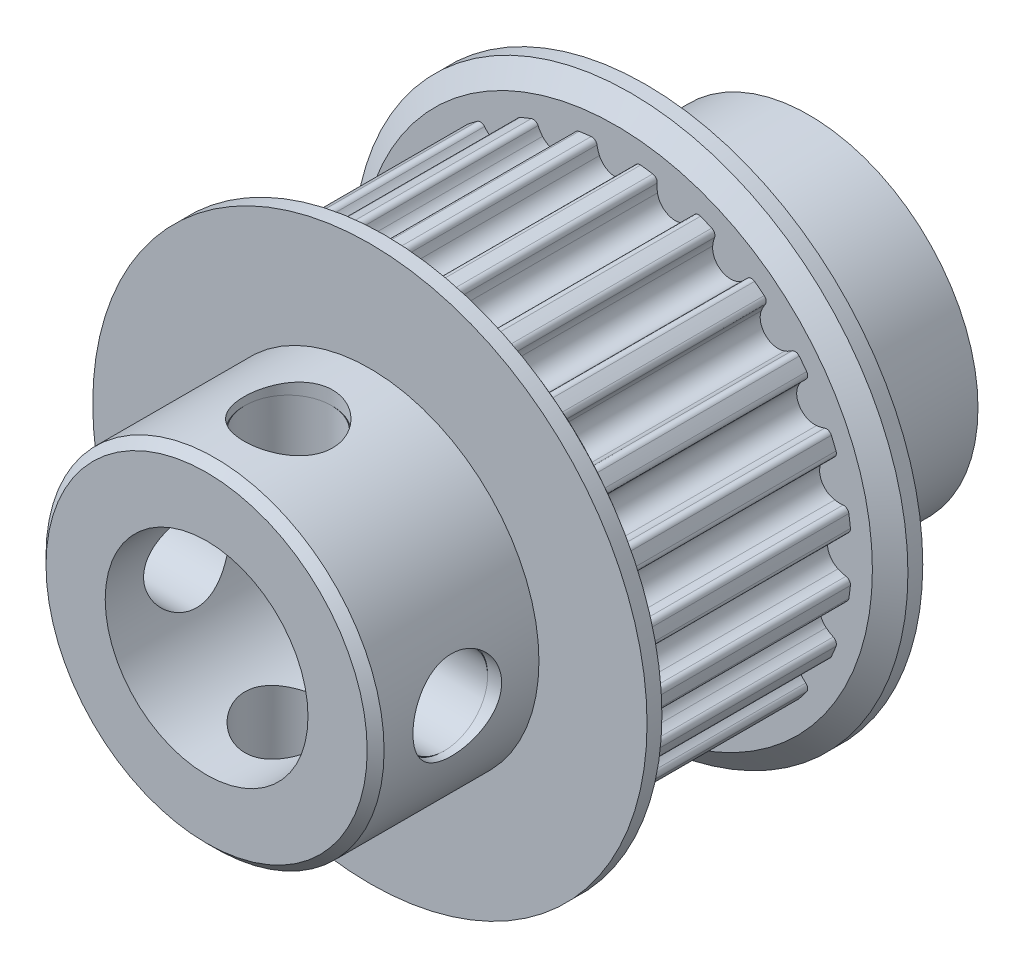
SolidWorks part; units mm, degrees
ref_plane "Front Plane" through (0, 0, 0) normal (0, 0, 1) x (1, 0, 0)
ref_plane "Top Plane" through (0, 0, 0) normal (0, 1, 0) x (1, 0, 0)
ref_plane "Right Plane" through (0, 0, 0) normal (1, 0, 0) x (0, 0, -1)
sketch "Sketch1" plane through (0, 0, 0) normal (0, 0, 1) x (1, 0, 0)
  line L1 (-2.6709, 9.9345) -> (2.6709, 9.9345) construction
  line L4 (0, 0) -> (0, 9.9345) construction
  line L5 (0, 9.9345) -> (0, 14.6065) construction
  line L6 (0, 11.4555) -> (2.9742, 11.0627) construction
  line L7 (2.9742, 11.0627) -> (4.1023, 10.7594) construction
  line L8 (2.9742, 11.0627) -> (2.6709, 9.9345) construction
  line L9 (-2.9742, 11.0627) -> (-2.6709, 9.9345) construction
  line L10 (-2.8753, 10.6947) -> (-3.4997, 13.0175)
  line L11 (-3.4997, 13.0175) -> (3.4997, 13.0175)
  line L12 (3.4997, 13.0175) -> (2.8753, 10.6947)
  circle A0 centre (0, 0) radius 11.4555 construction
  circle A1 centre (0, 0) radius 13.0175 construction
  circle A2 centre (0, 0) radius 11.0745 construction
  arc A3 (-0.7739, 10.4329) -> (0.7739, 10.4329) centre (0, 10.7845) ccw
  arc A4 (-0.7739, 10.4329) -> (-0.8885, 10.8068) centre (0.61, 11.0616) cw
  arc A5 (-2.8753, 10.6947) -> (-1.1612, 11.0135) centre (0, 0) cw
  arc A6 (-0.8885, 10.8068) -> (-1.1612, 11.0135) centre (-1.1349, 10.7648) ccw
  arc A7 (2.8753, 10.6947) -> (1.1612, 11.0135) centre (0, 0) ccw
  arc A8 (0.8885, 10.8068) -> (1.1612, 11.0135) centre (1.1349, 10.7648) cw
  arc A9 (0.7739, 10.4329) -> (0.8885, 10.8068) centre (-0.61, 11.0616) ccw
  point P6 (0, 20.9083)
  point P11 (0, 11.4555)
  point P13 (0, 13.0175)
  point P14 (0, 11.0745)
  dimension "D1" = 6.3018
  dimension "D2" = 3.151
sketch "Sketch2" plane through (0, 0, 0) normal (1, 0, 0) x (0, 0, -1)
  line L0 (-10.31, 3.175) -> (10.31, 3.175)
  line L1 (-10.31, 3.175) -> (-10.31, 7.94)
  line L2 (-10.31, 7.94) -> (-2.64, 7.94)
  line L3 (-2.64, 7.94) -> (-2.64, 13.0175)
  line L4 (-2.64, 13.0175) -> (-1.245, 13.0175) construction
  line L5 (-1.245, 13.0175) -> (-1.245, 11.0745) construction
  line L6 (-1.245, 11.0745) -> (8.915, 11.0745)
  line L7 (8.915, 11.0745) -> (8.915, 13.0175) construction
  line L8 (8.915, 13.0175) -> (10.31, 13.0175) construction
  line L9 (10.31, 13.0175) -> (10.31, 3.175)
  line L10 (-10.31, 0) -> (10.31, 0) construction
  line L11 (9.6125, 13.0175) -> (8.915, 12.046)
  line L12 (-1.245, 12.046) -> (-1.9425, 13.0175)
  line L13 (-2.64, 13.0175) -> (-1.9425, 13.0175)
  line L14 (-1.245, 12.046) -> (-1.245, 11.0745)
  line L15 (8.915, 11.0745) -> (8.915, 12.046)
  line L16 (9.6125, 13.0175) -> (10.31, 13.0175)
  arc A0 (-1.245, 12.046) -> (-1.9425, 13.0175) centre (-2.2703, 12.046) ccw construction
  arc A1 (8.915, 12.046) -> (9.6125, 13.0175) centre (9.9403, 12.046) cw construction
  point P12 (-1.245, 12.046)
  point P14 (-1.9425, 13.0175)
  point P20 (8.915, 12.046)
  point P21 (9.6125, 13.0175)
  point P25 (8.915, 0)
  point P26 (-1.245, 0)
revolve "Revolve1" add sketch "Sketch2" angle 360 mid plane about L10
sketch "Sketch3" plane through (0, 0, 0) normal (0, 0, 1) x (1, 0, 0)
  line L6 (3.4997, 13.0175) -> (-3.4997, 13.0175)
  line L7 (2.8753, 10.6947) -> (3.4997, 13.0175)
  line L8 (-3.4997, 13.0175) -> (-2.8753, 10.6947)
  line L9 (3.4997, 13.0175) -> (-3.4997, 13.0175)
  line L10 (2.8753, 10.6947) -> (3.4997, 13.0175)
  line L11 (-3.4997, 13.0175) -> (-2.8753, 10.6947)
  arc A8 (2.8753, 10.6947) -> (1.1612, 11.0135) centre (0, 0) ccw
  arc A9 (1.1612, 11.0135) -> (0.8885, 10.8068) centre (1.1349, 10.7648) ccw
  arc A10 (0.7739, 10.4329) -> (0.8885, 10.8068) centre (-0.61, 11.0616) ccw
  arc A11 (-0.7739, 10.4329) -> (0.7739, 10.4329) centre (0, 10.7845) ccw
  arc A12 (-0.8885, 10.8068) -> (-0.7739, 10.4329) centre (0.61, 11.0616) ccw
  arc A13 (-0.8885, 10.8068) -> (-1.1612, 11.0135) centre (-1.1349, 10.7648) ccw
  arc A14 (-1.1612, 11.0135) -> (-2.8753, 10.6947) centre (0, 0) ccw
  arc A15 (2.8753, 10.6947) -> (1.1612, 11.0135) centre (0, 0) ccw
  arc A16 (1.1612, 11.0135) -> (0.8885, 10.8068) centre (1.1349, 10.7648) ccw
  arc A17 (0.7739, 10.4329) -> (0.8885, 10.8068) centre (-0.61, 11.0616) ccw
  arc A18 (-0.7739, 10.4329) -> (0.7739, 10.4329) centre (0, 10.7845) ccw
  arc A19 (-0.8885, 10.8068) -> (-0.7739, 10.4329) centre (0.61, 11.0616) ccw
  arc A20 (-0.8885, 10.8068) -> (-1.1612, 11.0135) centre (-1.1349, 10.7648) ccw
  arc A21 (-1.1612, 11.0135) -> (-2.8753, 10.6947) centre (0, 0) ccw
  dimension "D1" = 0
extrude "Cut-Extrude1" cut sketch "Sketch3" against normal up to vertex (8.915 mm away) from vertex up to point (0, 11.0745, -8.915) starting at point (0, 11.0745, 1.245)
pattern_circular "CirPattern1" count 24 over 360 about axis through (0, 0, 10.31) along (0, 0, 1) of "Cut-Extrude1"
sketch "Sketch4" plane through (0, 0, 0) normal (1, 0, 0) x (0, -1, 0)
  line L0 (0, -2.64) -> (0, -10.31) construction
  line L1 (-7.94, -2.64) -> (7.94, -2.64) construction
  line L2 (-7.94, -10.31) -> (7.94, -10.31) construction
  circle A0 centre (0, -6.475) radius 2.0828
extrude "Cut-Extrude2" cut sketch "Sketch4" along normal through all
ref_plane "Plane1" through (0, 0, 6.475) normal (0, 0, 1) x (1, 0, 0)
sketch "Sketch5" plane through (0, 0, 6.475) normal (0, 0, 1) x (1, 0, 0)
  line L0 (0, 0.1664) -> (0, 7.94) construction
  line L1 (3.175, -1.7018) -> (3.175, 0)
  line L2 (3.556, -2.0828) -> (7.281, -2.0828)
  line L3 (3.175, 0) -> (7.94, 0) construction
  line L4 (3.175, 0) -> (7.662, 0)
  line L5 (7.662, 0) -> (7.662, -1.7018)
  line L6 (3.556, -2.0828) -> (3.175, -1.7018)
  line L7 (7.662, -1.7018) -> (7.281, -2.0828)
  circle A0 centre (0, 0) radius 7.94 construction
  circle A1 centre (0, 0) radius 3.175 construction
  point P2 (3.175, -2.0828)
  point P11 (7.662, -2.0828)
revolve "Revolve2" add sketch "Sketch5" angle 360 mid plane about L4
sketch "Sketch6" plane through (7.662, 5.3841, 0) normal (-1, 0, 0) x (0, -1, 0)
  line L1 (5.3841, 7.6775) -> (4.3427, 7.0763)
  line L2 (4.3427, 7.0763) -> (4.3427, 5.8737)
  line L3 (4.3427, 5.8737) -> (5.3841, 5.2725)
  line L4 (5.3841, 5.2725) -> (6.4255, 5.8737)
  line L5 (6.4255, 5.8737) -> (6.4255, 7.0763)
  line L6 (6.4255, 7.0763) -> (5.3841, 7.6775)
  circle A0 centre (5.3841, 6.475) radius 1.0414 construction
  dimension "D1" = 2.0828
extrude "Cut-Extrude3" cut sketch "Sketch6" along normal blind 1.5621
pattern_circular "CirPattern2" count 2 over 90 about axis through (0, 0, 10.31) along (0, 0, 1) of "Cut-Extrude2", "Revolve2", "Cut-Extrude3"
chamfer "Chamfer1" distance 0.397 angle 45 2 edges at (3.175, 0, 10.31) (7.94, 0, 10.31)
ref_axis "Center Axis 1" through (0, 0, -10.31) along (0, 0, 1)
ref_plane "Contact Plane 1" through (0, 0, 10.31) normal (0, 0, 1) x (1, 0, 0)
ref_plane "Contact Plane 2" through (0, 0, -10.31) normal (0, 0, -1) x (-1, 0, 0)
sketch "Sketch7" plane through (0, 0, 10.31) normal (0, 0, 1) x (1, 0, 0)
  circle A0 centre (0, 0) radius 4.7625
  dimension "D1" = 9.525
sketch "Sketch8" plane through (0, 0, -10.31) normal (0, 0, -1) x (-1, 0, 0)
  circle A0 centre (0, 0) radius 7.94
  dimension "D1" = 15.8801
extrude "Boss-Extrude1" add sketch "Sketch8" along normal blind 7.6708 contours A0
sketch "Sketch9" plane through (0, 0, 10.31) normal (0, 0, 1) x (1, 0, 0)
  circle A0 centre (0, 0) radius 4.7625
  dimension "D1" = 9.525
extrude "Cut-Extrude6" cut sketch "Sketch9" against normal through all both and the other way through all
sketch "Sketch10" plane through (7.662, 0, 0) normal (1, 0, 0) x (0, 0, -1)
  circle A0 centre (-6.475, 0) radius 2.032
  dimension "D1" = 4.064
extrude "Cut-Extrude7" cut sketch "Sketch10" against normal through all both and the other way through all
sketch "Sketch11" plane through (0, 7.662, 0) normal (0, 1, 0) x (1, 0, 0)
  circle A0 centre (0, -6.475) radius 2.032
  dimension "D1" = 4.064
extrude "Cut-Extrude8" cut sketch "Sketch11" against normal blind 20.828
equation "\"D2@Sketch1\" = \"D1@Sketch1\"/2"
equation "\"D1@Sketch6\" = \"Set Screw@Sketch4\" / 2"
equation "\"D1@Cut-Extrude3\" = \"D1@Sketch6\"*.75"
equation "\"D1@Chamfer1\"=\"Hub Dia@Sketch2\"*.025"
